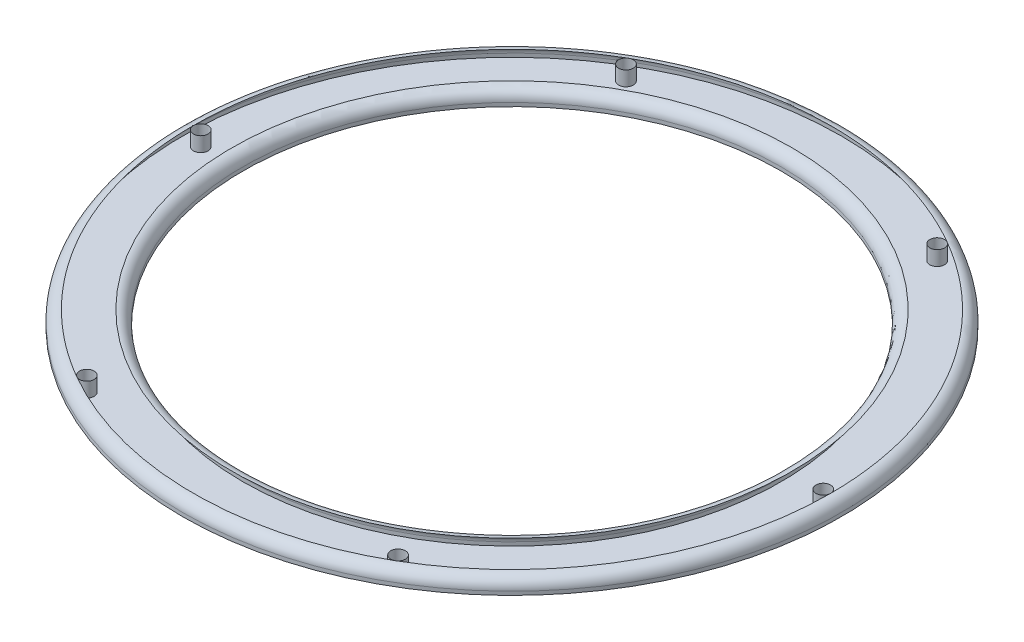
SolidWorks part; units mm, degrees
ref_plane "Front Plane" through (0, 0, 0) normal (0, 0, 1) x (1, 0, 0)
ref_plane "Top Plane" through (0, 0, 0) normal (0, 1, 0) x (1, 0, 0)
ref_plane "Right Plane" through (0, 0, 0) normal (1, 0, 0) x (0, 0, -1)
sketch "Sketch1" plane through (0, 0, 0) normal (0, 0, 1) x (1, 0, 0)
  line L0 (0, 0) -> (0, 45.0263) construction
  line L2 (-73.5, 0) -> (-90, 0)
  line L3 (-73.5, 0) -> (-73.5, 1)
  line L4 (-76.5, 4) -> (-87, 4)
  line L5 (-90, 0) -> (-90, 1)
  arc A0 (-76.5, 4) -> (-73.5, 1) centre (-76.5, 1) cw
  arc A1 (-87, 4) -> (-90, 1) centre (-87, 1) ccw
  point P11 (-90, 4)
  dimension "D4" = 3
  dimension "D1" = 4
  dimension "D2" = 147
  dimension "D3" = 180
revolve "Revolve1" add sketch "Sketch1" angle 360 about L0
sketch "Sketch2" plane through (0, 4, 0) normal (0, 1, 0) x (1, 0, 0)
  circle A0 centre (-85, 0) radius 2
  dimension "D2" = 4
  dimension "D1" = 85
extrude "Cut-Extrude1" cut sketch "Sketch2" against normal through all
pattern_circular "CirPattern1" count 6 over 360 about axis through (0, 0, 0) along (0, -1, 0) of "Cut-Extrude1" reverse direction yes
